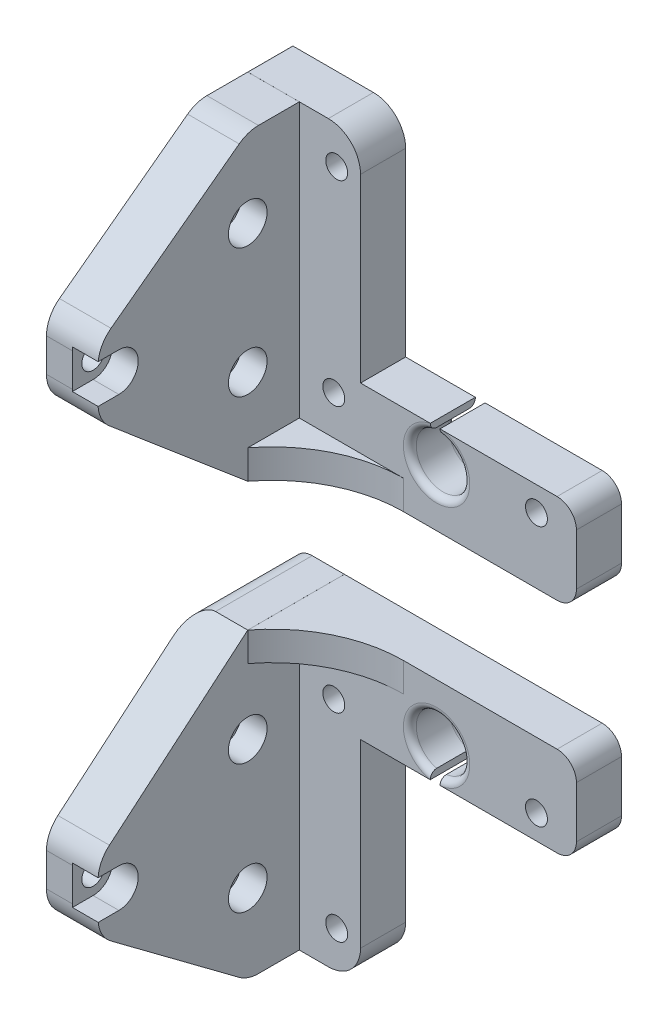
SolidWorks part; units mm, degrees
material "ABS"
ref_plane "Front Plane" through (0, 0, 0) normal (0, 0, 1) x (1, 0, 0)
ref_plane "Top Plane" through (0, 0, 0) normal (0, 1, 0) x (1, 0, 0)
ref_plane "Right Plane" through (0, 0, 0) normal (1, 0, 0) x (0, 0, -1)
ref_plane "Plane5" through (60, 0, 0) normal (1, 0, 0) x (0, 0, -1)
sketch "Sketch50" plane through (60, 0, 0) normal (1, 0, 0) x (0, 0, -1)
  line L0 (-38.2349, -28) -> (-38.2349, -38)
  line L1 (0, -55.3249) -> (-15, -55.3249)
  line L2 (0, -8.3249) -> (-15, -8.3249)
  line L4 (0, -55.3249) -> (0, -8.3249)
  line L5 (-15, -2.0171) -> (-15, -57.8143) construction
  line L9 (-38.2349, -28) -> (-15, -8.3249)
  line L10 (-38.2349, -38) -> (-15, -55.3249)
  circle A0 centre (-35, -33) radius 1.75
  circle A1 centre (-15, -23) radius 1.75
  circle A2 centre (-15, -43) radius 1.75
  dimension "D1" = 3.5
  dimension "D2" = 3.5
  dimension "D3" = 3.5
  dimension "D4" = 20
  dimension "D5" = 20
  dimension "D6" = 47
  dimension "D7" = 15
  dimension "D8" = 10
extrude "Extrude1" add sketch "Sketch50" along normal blind 8 separate body
sketch "Sketch52" plane through (0, 0, 0) normal (0, 0, -1) x (-1, 0, 0)
  line L0 (-60.0211, -55.3284) -> (-60.0211, -8.3284)
  line L1 (-111, -8.3284) -> (-111, -22.2806)
  line L2 (-60.0211, -8.3284) -> (-111, -8.3284)
  line L3 (-77.5, -22.2806) -> (-111, -22.2806)
  line L4 (-60.0211, -55.3284) -> (-77.5, -55.3284)
  line L5 (-77.5, -55.3249) -> (-77.5, -8.3249)
  line L6 (-77.5, -55.3284) -> (-77.5, -22.2806)
  circle A0 centre (-89.3, -17.2) radius 4.15
  circle A1 centre (-73.3515, -18.9313) radius 1.7
  circle A2 centre (-104.8, -18.5) radius 1.7
  circle A3 centre (-73.8015, -49.5086) radius 1.7
  point P3 (-113, -87.5802)
  point P9 (-74.0211, -54.9585)
  point P10 (-74.0211, -7.7617)
  dimension "D2" = 47
  dimension "D4" = 3.4
  dimension "D3" = 8.3
  dimension "D1" = 9.5
extrude "Extrude2" add sketch "Sketch52" against normal blind 7
fillet "Fillet1" radius 3 2 edges at (111, -22.2806, 3.5) (111, -8.3284, 3.5)
fillet "Fillet2" radius 5 1 edges at (77.5, -55.3284, 3.5)
sketch "Sketch54" plane through (0, -8.3284, 0) normal (0, 1, 0) x (1, 0, 0)
  line L0 (68, -7) -> (108, -7) construction
  line L1 (68, -15) -> (68, -7)
  line L2 (68, -15) -> (68, -38.2349) construction
  line L3 (68, 0) -> (68, -15) construction
  line L4 (68, -7) -> (84.1795, -7)
  arc A0 (84.1795, -7) -> (68, -15) centre (84.1795, -27.3609) ccw
extrude "Extrude3" add sketch "Sketch54" against normal blind 4.5
fillet "Fillet4" radius 5 3 edges at (64, -28, 38.2349) (64, -38, 38.2349) (64, -55.3249, 15)
fillet "Fillet5" radius 3 1 edges at (60, -8.3249, 7.5)
sketch "Sketch55" plane through (68, 0, 0) normal (1, 0, 0) x (0, 0, -1)
  line L0 (-35, -30) -> (-38.7879, -30)
  line L1 (-38.7879, -30) -> (-38.7879, -36)
  line L2 (-35, -36) -> (-38.7879, -36)
  arc A0 (-35, -36) -> (-35, -30) centre (-35, -33) ccw
  circle A1 centre (-15, -23) radius 3
  circle A2 centre (-15, -43) radius 3
  dimension "D1" = 6
  dimension "D2" = 6
  dimension "D3" = 6
extrude "Cut-Extrude3" cut sketch "Sketch55" against normal blind 4
sketch "Sketch56" plane through (0, 0, 0) normal (0, 0, -1) x (-1, 0, 0)
  line L0 (-108, -22.2806) -> (-77.5, -22.2806) construction
  line L1 (-89.3173, -23.6005) -> (-88.3204, -23.6005)
  line L2 (-89.3173, -23.6005) -> (-89.3173, -20.9607)
  line L3 (-89.3173, -20.9607) -> (-88.3204, -20.9607)
  line L4 (-88.3204, -23.6005) -> (-88.3204, -20.9607)
  line L5 (-89.3173, -23.6005) -> (-88.3204, -20.9607) construction
  line L6 (-89.3173, -20.9607) -> (-88.3204, -23.6005) construction
  point P0 (-88.8189, -22.2806)
fillet "Fillet9" radius 1 1 edges at (89.3, -13.05, 0)
fillet "Fillet10" radius 1 1 edges at (89.3, -13.05, 7)
sketch "Sketch57" plane through (0, -22.2806, 0) normal (0, -1, 0) x (1, 0, 0)
  line L0 (88.8276, 7.5275) -> (89.8276, 7.5275)
  line L2 (89.8276, -0.6284) -> (89.8276, 7.5275)
  line L3 (88.8276, -0.6284) -> (88.8276, 7.5275)
  line L4 (88.8276, -0.6284) -> (89.8276, -0.6284)
extrude "Extrude4" cut sketch "Sketch57" against normal blind 4
ref_plane "Plane6" through (0, 1.6716, 0) normal (0, 1, 0) x (1, 0, 0)
extrude "Cut-Extrude4" cut sketch "Sketch56" against normal up to surface (7 mm away) up to face at (84.7186, -28.299, 7)
mirror "Mirror1" about plane through (0, 1.6716, 0) normal (0, 1, 0) of bodies 133
